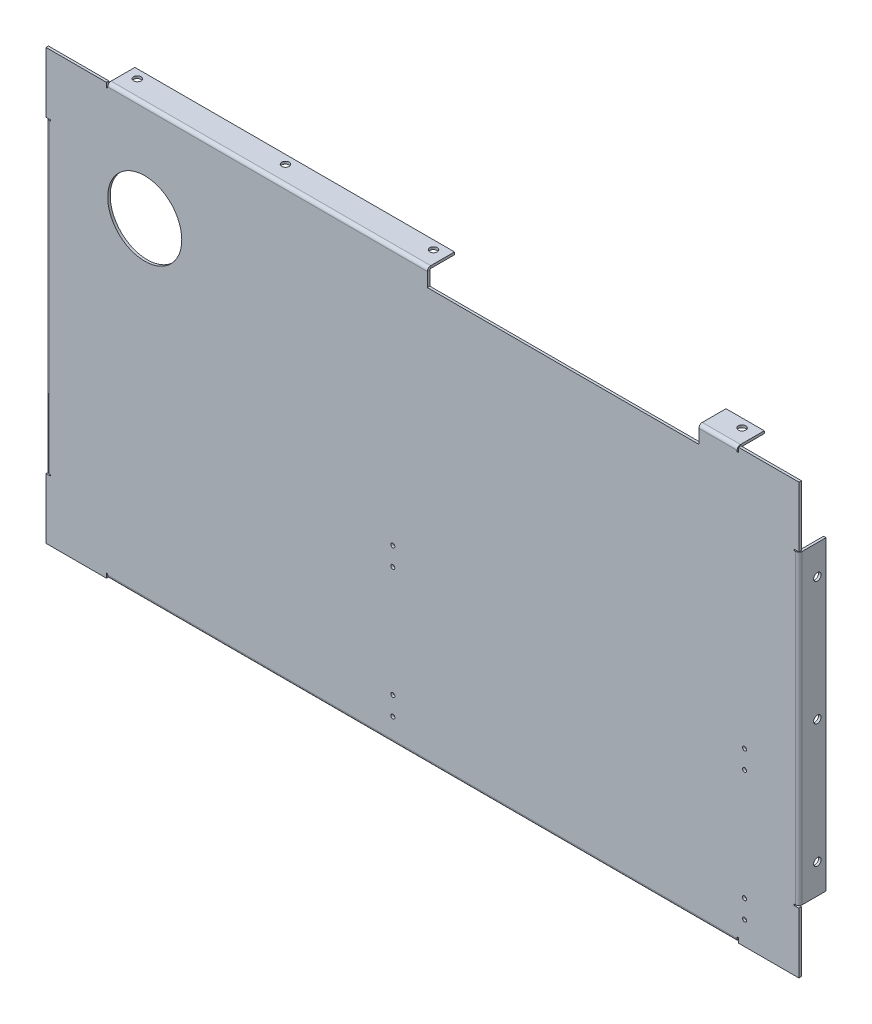
SolidWorks part; units mm, degrees
note: The reader was unsure of these and kept them because the rebuilt part matched: flange length of "边线-法兰1", "边线-法兰2", "边线-法兰3", "边线-法兰4", "边线-法兰5".
ref_plane "前视基准面" through (0, 0, 0) normal (0, 0, 1) x (1, 0, 0)
ref_plane "上视基准面" through (0, 0, 0) normal (0, 1, 0) x (1, 0, 0)
ref_plane "右视基准面" through (0, 0, 0) normal (1, 0, 0) x (0, 0, -1)
sketch "草图1" plane through (0, 0, 0) normal (0, 0, 1) x (1, 0, 0)
  line L0 (224, 174) -> (305, 174)
  line L1 (-305, 174) -> (4, 174)
  line L2 (-305, 174) -> (-305, -174)
  line L3 (-305, -174) -> (305, -174)
  line L4 (305, 174) -> (305, -174)
  line L5 (-305, 174) -> (305, -174) construction
  line L6 (-305, -174) -> (305, 174) construction
  line L8 (4, 174) -> (4, 160)
  line L9 (4, 160) -> (224, 160)
  line L10 (224, 174) -> (224, 160)
  point P0 (0, 0)
  dimension "D1" = 610
  dimension "D2" = 348
  dimension "D3" = 309
  dimension "D4" = 220
  dimension "D5" = 14
sheet metal parameters "钣金1" thickness 2 parameters "D1"=0.7366
base flange "基体-法兰1" sketch "草图1" thickness 2 reverse thickness direction no parameters "D1"=0.7366
edge flange "边线-法兰1" sketch "草图5" flange angle 90 flange length 22 flange position material inside bend radius 0.7366 thickness 2 relief rectangular parameters "D6"=10
sketch "草图5" plane through (305, 0, -2) normal (1, 0, 0) x (0, -1, 0)
  line L2 (-124, 0) -> (-124, 20)
  line L3 (-124, 20) -> (124, 20)
  line L4 (124, 20) -> (124, 0)
  line L5 (174, 0) -> (-174, 0) construction
  line L6 (124, 0) -> (-124, 0)
  line L7 (-174, 0) -> (-174, -2) construction
  line L8 (174, 0) -> (174, -2) construction
  line L9 (174, -2) -> (-174, -2) construction
  dimension "D1" = 50
  dimension "D2" = 50
  dimension "D3" = 22
bend "边线折弯1" bend radius 0.7366 bend angle 90 parameters "D5"=1
edge flange "边线-法兰2" sketch "草图8" flange angle 90 flange length 22 flange position material inside bend radius 0.7366 thickness 2 relief rectangular parameters "D6"=10
sketch "草图8" plane through (0, -174, -2) normal (0, -1, 0) x (-1, 0, 0)
  line L0 (305, 0) -> (-305, 0) construction
  line L1 (255, 0) -> (-255, 0)
  line L2 (-255, 0) -> (-255, 20)
  line L3 (-255, 20) -> (255, 20)
  line L4 (255, 20) -> (255, 0)
  line L5 (305, 0) -> (305, -2) construction
  line L6 (-305, 0) -> (-305, -2) construction
  line L7 (305, -2) -> (-305, -2) construction
  dimension "D1" = 50
  dimension "D2" = 50
  dimension "D3" = 22
bend "边线折弯2" bend radius 0.7366 bend angle 90 parameters "D5"=2
edge flange "边线-法兰3" sketch "草图11" flange angle 90 flange length 22 flange position material inside bend radius 0.7366 thickness 2 relief rectangular parameters "D6"=10
sketch "草图11" plane through (-305, 0, -2) normal (-1, 0, 0) x (0, 1, 0)
  line L0 (174, 0) -> (-174, 0) construction
  line L1 (124, 0) -> (-124, 0)
  line L2 (-124, 0) -> (-124, 20)
  line L3 (-124, 20) -> (124, 20)
  line L4 (124, 20) -> (124, 0)
  line L5 (-174, 0) -> (-174, -2) construction
  line L6 (174, 0) -> (174, -2) construction
  line L7 (174, -2) -> (-174, -2) construction
  dimension "D1" = 50
  dimension "D2" = 50
  dimension "D3" = 22
bend "边线折弯3" bend radius 0.7366 bend angle 90 parameters "D5"=3
edge flange "边线-法兰4" sketch "草图14" flange angle 90 flange length 22 flange position material inside bend radius 0.7366 thickness 2 relief rectangular parameters "D6"=10
sketch "草图14" plane through (0, 174, -2) normal (0, 1, 0) x (1, 0, 0)
  line L0 (305, 0) -> (224, 0) construction
  line L1 (255, 0) -> (224, 0)
  line L2 (224, 0) -> (224, 20)
  line L3 (224, 20) -> (255, 20)
  line L4 (255, 20) -> (255, 0)
  line L5 (305, 0) -> (305, -2) construction
  line L6 (305, -2) -> (224, -2) construction
  dimension "D1" = 50
  dimension "D2" = 22
bend "边线折弯4" bend radius 0.7366 bend angle 90 parameters "D5"=4
edge flange "边线-法兰5" sketch "草图17" flange angle 90 flange length 22 flange position material inside bend radius 0.7366 thickness 2 relief rectangular parameters "D6"=10
sketch "草图17" plane through (0, 174, -2) normal (0, 1, 0) x (1, 0, 0)
  line L0 (4, 0) -> (-305, 0) construction
  line L1 (4, 0) -> (-255, 0)
  line L2 (-255, 0) -> (-255, 20)
  line L3 (-255, 20) -> (4, 20)
  line L4 (4, 20) -> (4, 0)
  line L5 (-305, 0) -> (-305, -2) construction
  dimension "D1" = 50
bend "边线折弯5" bend radius 0.7366 bend angle 90 parameters "D5"=5
hole_wizard "M4 螺纹孔1" positions "草图19" profile "草图18" tap size "M4" standard "GB"
sketch "草图19" plane through (0, 0, 0) normal (0, 0, 1) x (1, 0, 0)
  line L0 (305, -174) -> (305, -125) construction
  line L1 (256, -174) -> (305, -174) construction
  point P0 (-24, -155)
  point P1 (-24, -140)
  point P3 (-24, -50)
  point P5 (-24, -35)
  point P7 (261, -155)
  point P9 (261, -140)
  point P11 (261, -50)
  point P13 (261, -35)
  dimension "D1" = 44
  dimension "D2" = 285
  dimension "D3" = 15
  dimension "D4" = 90
  dimension "D5" = 15
  dimension "D6" = 19
sketch "草图18" plane through (-24, -155, 0) normal (1, 0, 0) x (0, -1, 0)
  line L0 (0, 0) -> (0, 11.0914)
  line L1 (0, 11.0914) -> (1.65, 10.1)
  line L2 (1.65, 10.1) -> (1.65, 0)
  line L5 (1.65, 0) -> (0, 0)
  line L10 (0, 11.0914) -> (-1.65, 10.1) construction
  line L11 (0, -6.35) -> (0, 107.95) construction
  dimension "螺纹孔钻头直径" = 3.3
  dimension "螺纹孔钻头深度" = 10.1
  dimension "导头角度" = 118
cosmetic thread "孔螺蚊线1" parameters "D1"=2, "D2"=4
cosmetic thread "孔螺蚊线2" parameters "D1"=2, "D2"=4
cosmetic thread "孔螺蚊线3" parameters "D1"=2, "D2"=4
cosmetic thread "孔螺蚊线4" parameters "D1"=2, "D2"=4
cosmetic thread "孔螺蚊线5" parameters "D1"=2, "D2"=4
cosmetic thread "孔螺蚊线6" parameters "D1"=2, "D2"=4
cosmetic thread "孔螺蚊线7" parameters "D1"=2, "D2"=4
cosmetic thread "孔螺蚊线8" parameters "D1"=2, "D2"=4
sketch "草图20" plane through (305, 0, 0) normal (1, 0, 0) x (0, 0, -1)
  line L1 (0, 125) -> (0, 174) construction
  circle A0 centre (15, 0) radius 3
  circle A1 centre (15, 100) radius 3
  circle A2 centre (15, -100) radius 3
  dimension "D4" = 6
  dimension "D1" = 15
  dimension "D2" = 100
  dimension "D3" = 100
extrude "切除-拉伸1" cut sketch "草图20" against normal through all normal cut yes
sketch "草图21" plane through (0, -174, 0) normal (0, -1, 0) x (1, 0, 0)
  line L0 (-305, 0) -> (-256, 0) construction
  line L1 (-305, -2) -> (-305, 0) construction
  circle A0 centre (-246, -15) radius 3
  circle A1 centre (-126, -15) radius 3
  circle A2 centre (-6, -15) radius 3
  circle A3 centre (244, -15) radius 3
  circle A4 centre (119, -15) radius 3
  dimension "D7" = 6
  dimension "D1" = 15
  dimension "D2" = 59
  dimension "D3" = 120
  dimension "D4" = 120
  dimension "D5" = 125
  dimension "D6" = 125
extrude "切除-拉伸2" cut sketch "草图21" against normal through all normal cut yes
sketch "草图22" plane through (0, 0, 0) normal (0, 0, 1) x (1, 0, 0)
  line L0 (-256, 174) -> (-305, 174) construction
  line L1 (-305, 174) -> (-305, 125) construction
  circle A0 centre (-225, 94) radius 30
  dimension "D3" = 60
  dimension "D1" = 80
  dimension "D2" = 80
extrude "切除-拉伸3" cut sketch "草图22" against normal through all normal cut yes
flat pattern "平板型式1" [suppressed]
sketch "折弯-线1" plane through (0, 0, 0) normal (0, 1, 0) x (-1, 0, 0)
bend of the flat pattern "展开-<边线折弯1>1"
bend of the flat pattern "展开-<边线折弯2>1"
bend of the flat pattern "展开-<边线折弯3>1"
bend of the flat pattern "展开-<边线折弯4>1"
bend of the flat pattern "展开-<边线折弯5>1"
